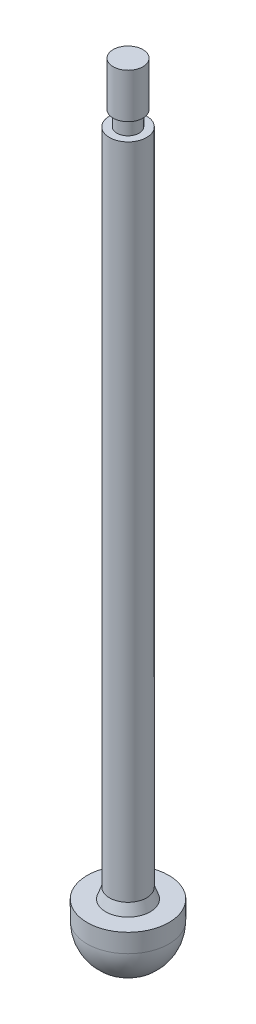
SolidWorks part; units mm, degrees
ref_plane "Front Plane" through (0, 0, 0) normal (0, 0, 1) x (1, 0, 0)
ref_plane "Top Plane" through (0, 0, 0) normal (0, 1, 0) x (1, 0, 0)
ref_plane "Right Plane" through (0, 0, 0) normal (1, 0, 0) x (0, 0, -1)
sketch "Sketch1" plane through (0, 0, 0) normal (0, 0, 1) x (1, 0, 0)
  line L0 (0, 0) -> (0, 100.5) construction
  line L1 (0, 0) -> (0, -5.5) construction
  line L2 (5.5, 0) -> (5.5, 2.5)
  line L3 (5.5, 2.5) -> (3, 2.5)
  line L4 (2.5, 3.8737) -> (2.5, 92.5)
  line L5 (2.5, 92.5) -> (1.5, 92.5)
  line L7 (2, 100.5) -> (0, 100.5)
  line L8 (0, 100.5) -> (0, -5.5)
  line L12 (2.5, 3.8737) -> (3, 2.5)
  line L13 (1.5, 92.5) -> (1.5, 94.5)
  line L14 (1.5, 94.5) -> (2, 94.5)
  line L15 (2, 94.5) -> (2, 100.5)
  arc A0 (0, -5.5) -> (5.5, 0) centre (0, 0) ccw
  dimension "D1" = 5.5
  dimension "D2" = 2.5
  dimension "D3" = 8
  dimension "D4" = 2
  dimension "D5" = 8
  dimension "D6" = 3
  dimension "D7" = 110
  dimension "D8" = 90
  dimension "D9" = 2
  dimension "D10" = 1.5
revolve "Revolve1" add sketch "Sketch1" angle 360 about L0
ref_point "Point1"
